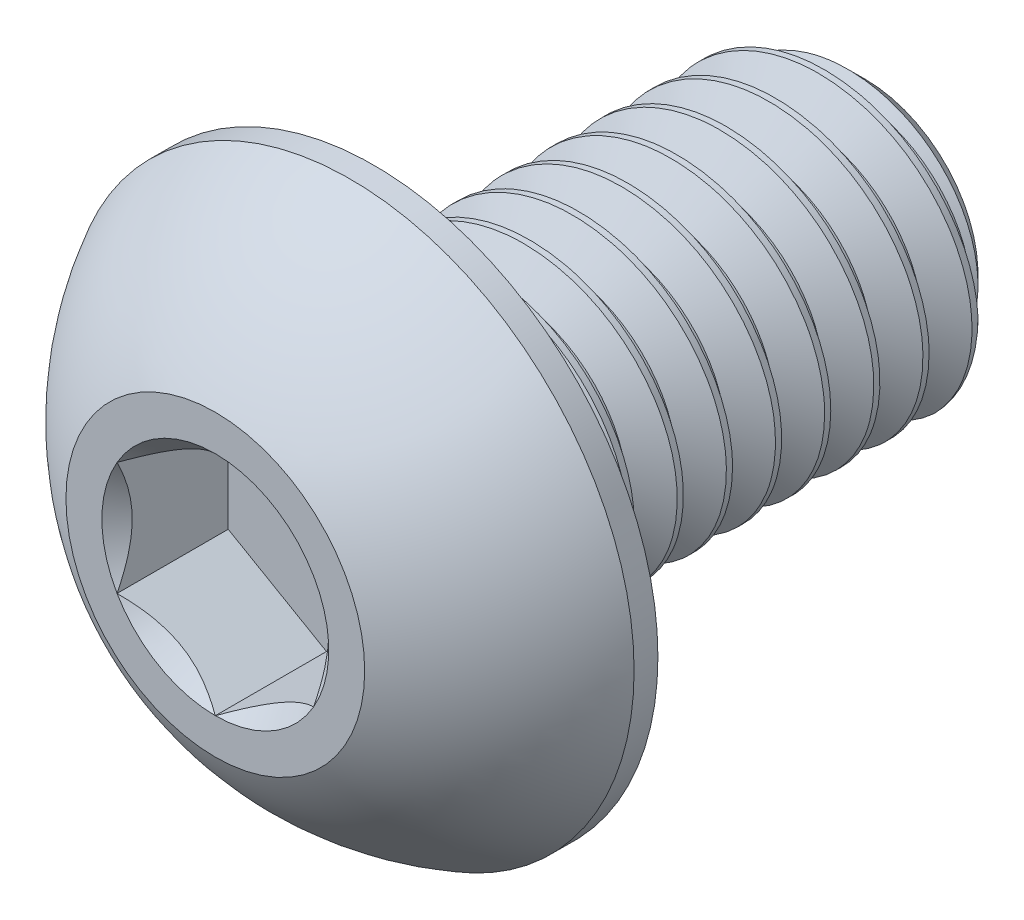
SolidWorks part; units mm, degrees
ref_plane "Front" through (0, 0, 0) normal (0, 0, 1) x (1, 0, 0)
ref_plane "Top" through (0, 0, 0) normal (0, 1, 0) x (1, 0, 0)
ref_plane "Right" through (0, 0, 0) normal (1, 0, 0) x (0, 0, -1)
sketch "Sketch1" plane through (0, 0, 0) normal (1, 0, 0) x (0, 0, -1)
  line L2 (2.5654, 2.413) -> (10.5029, 2.413)
  line L3 (10.5029, 2.413) -> (10.5029, 0)
  line L4 (10.5029, 0) -> (2.5654, 0)
  line L6 (2.1806, 4.5847) -> (2.5654, 4.5847) construction
  line L7 (10.5029, 2.413) -> (10.5029, -2.413) construction
  line L8 (0, 0) -> (2.5654, 0) construction
  line L9 (2.5654, 4.5847) -> (2.5654, -4.5847) construction
  line L11 (2.5654, 2.413) -> (2.5654, 0)
  line L13 (0, 1.5875) -> (0, -1.5875) construction
  line L14 (0, 1.5875) -> (0, 2.413) construction
  arc A3 (0, 2.413) -> (2.1806, 4.5847) centre (4.5749, 0) cw construction
  dimension "D1" = 0.3848
  dimension "Head Ht" = 2.5654
  dimension "Head Dia" = 9.1694
  dimension "Dia" = 4.826
  dimension "Lg" = 7.9375
  dimension "Hex" = 3.175
revolve "Revolve1" add sketch "Sketch1" angle 360 mid plane about L4
sketch "Sketch3" plane through (0, 0, -10.5029) normal (0, 0, -1) x (-1, 0, 0)
  circle A0 centre (0, 0) radius 2.413
curve "Helix/Spiral1" pitch 0.7937 height 8.7312 turns 11
sketch "Sketch2" plane through (0, 0, 0) normal (1, 0, 0) x (0, 0, -1)
  line L0 (10.5029, 2.413) -> (11.1974, 2.413)
  line L1 (11.1974, 2.413) -> (10.8998, 1.8974)
  line L2 (10.8998, 1.8974) -> (10.8006, 1.8974)
  line L3 (10.8006, 1.8974) -> (10.5029, 2.413)
  line L4 (10.6517, 2.1552) -> (11.0486, 2.1552) construction
  dimension "D1" = 60
  dimension "D2" = 0.0992
  dimension "D3" = 0.3969
chamfer "Chamfer1" distance 0.5953 angle 45 1 edges at (0, 2.413, -10.5029)
sweep "Cut-Sweep1" cut profiles "Sketch2" path "Helix/Spiral1"
sketch "Sketch7" plane through (0, 0, 0) normal (1, 0, 0) x (0, 0, -1)
  line L6 (2.1806, 4.5847) -> (2.5654, 4.5847) construction
  line L8 (0, 0) -> (2.5654, 0) construction
  line L11 (2.5654, 4.5847) -> (2.5654, -4.5847) construction
  line L12 (2.1806, 4.5847) -> (2.5654, 4.5847)
  line L13 (0, 0) -> (2.5654, 0)
  line L14 (0, 1.5875) -> (0, -1.5875) construction
  line L15 (2.5654, 4.5847) -> (2.5654, 0)
  line L16 (0, 2.413) -> (0, 0)
  arc A2 (2.1806, 4.5847) -> (0, 2.413) centre (4.5749, 0) ccw construction
  arc A3 (2.1806, 4.5847) -> (0, 2.413) centre (4.5749, 0) ccw
revolve "Revolve2" add sketch "Sketch7" angle 360 mid plane about L13
sketch "Sketch5" plane through (0, 0, 0) normal (0, 0, 1) x (1, 0, 0)
  line L1 (1.5875, -0.9165) -> (1.5875, 0.9165)
  line L2 (1.5875, 0.9165) -> (0, 1.8331)
  line L3 (0, 1.8331) -> (-1.5875, 0.9165)
  line L4 (-1.5875, 0.9165) -> (-1.5875, -0.9165)
  line L5 (-1.5875, -0.9165) -> (0, -1.8331)
  line L6 (0, -1.8331) -> (1.5875, -0.9165)
  circle A0 centre (0, 0) radius 1.5875 construction
extrude "Cut-Extrude2" cut sketch "Sketch5" against normal blind 1.7958
sketch "Sketch6" plane through (0, 0, 0) normal (0, 0, 1) x (1, 0, 0)
  circle A0 centre (0, 0) radius 1.8331
extrude "Cut-Extrude3" cut sketch "Sketch6" against normal blind 1.7958 draft 45
sketch "Sketch9" [suppressed] plane through (0, 0, -2.2098) normal (0, 0, 1) x (1, 0, 0)
  circle A2 centre (0, 0) radius 2.0828
extrude "Boss-Extrude2" [suppressed] add sketch "Sketch9" against normal offset from surface (3.175 mm away) 22.225
sketch "Sketch10" plane through (0, 0, 0) normal (1, 0, 0) x (0, 0, -1)
  line L0 (10.5029, 2.413) -> (10.5029, -2.413) construction
  point P0 (9.3123, -2.413)
  dimension "D1" = 1.1906
equation "\"D3@Helix/Spiral1\" = \"Lg@Sketch1\" + \"D4@Helix/Spiral1\""
equation "\"D2@Sketch2\" = \"D4@Helix/Spiral1\" * .125"
equation "\"D3@Sketch2\" = \"D4@Helix/Spiral1\" * .5"
equation "\"D1@Chamfer1\" = \"D4@Helix/Spiral1\" * .75"
equation "\"D1@Cut-Extrude2\" = \"Head Ht@Sketch1\" * .7"
equation "\"D1@Sketch1\" = \"Head Ht@Sketch1\" * .15"
equation "\"D1@Sketch10\" = \"D4@Helix/Spiral1\" * 1.5"
equation "\"D1@Cut-Extrude3\" = \"D1@Cut-Extrude2\""
